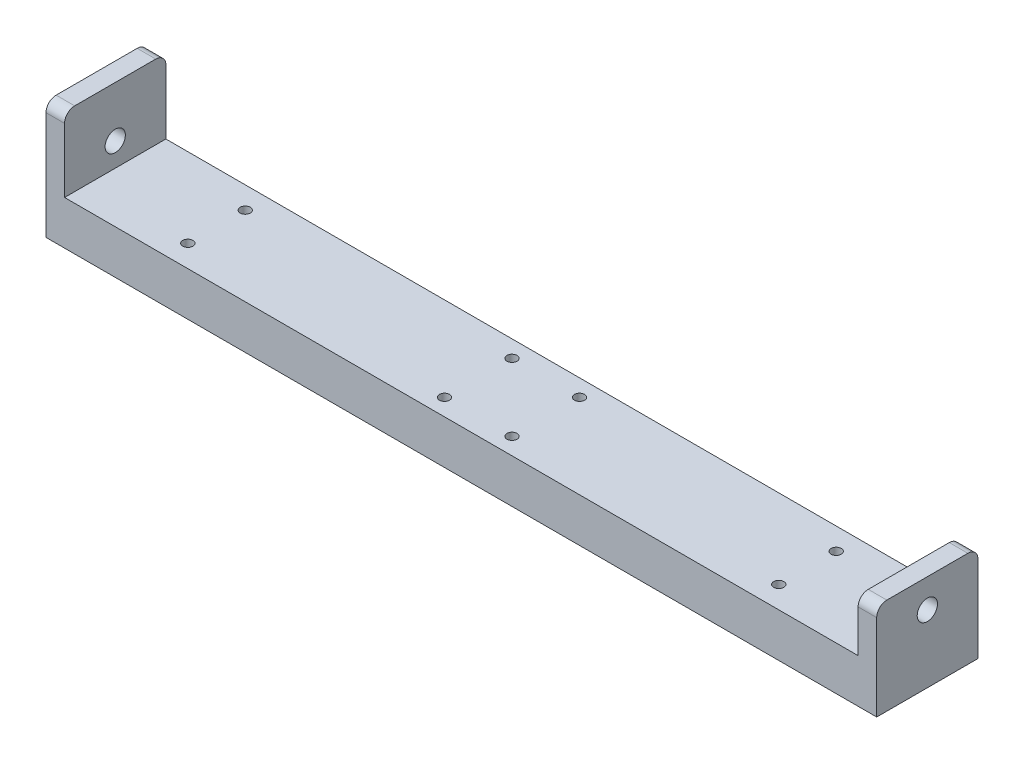
SolidWorks part; units mm, degrees
material "普通碳钢"
ref_plane "前视基准面" through (0, 0, 0) normal (0, 0, 1) x (1, 0, 0)
ref_plane "上视基准面" through (0, 0, 0) normal (0, 1, 0) x (1, 0, 0)
ref_plane "右视基准面" through (0, 0, 0) normal (1, 0, 0) x (0, 0, -1)
sketch "草图1" plane through (0, 0, 0) normal (0, 0, 1) x (1, 0, 0)
  line L0 (0, 0) -> (246, 0)
  line L1 (246, 0) -> (246, 28.5)
  line L2 (246, 28.5) -> (240.5, 28.5)
  line L3 (240.5, 28.5) -> (240.5, 13)
  line L4 (240.5, 13) -> (5.5, 13)
  line L5 (5.5, 13) -> (5.5, 35)
  line L6 (5.5, 35) -> (0, 35)
  line L7 (0, 35) -> (0, 0)
  dimension "D1" = 5.5
  dimension "D2" = 35
  dimension "D3" = 28.5
  dimension "D4" = 13
  dimension "D5" = 246
  dimension "D6" = 5.5
extrude "凸台-拉伸1" add sketch "草图1" along normal mid plane 30
sketch "草图2" plane through (0, 13, 0) normal (0, 1, 0) x (1, 0, 0)
  line L0 (0, 0) -> (246, 0) construction
  line L1 (246, -15) -> (246, 15) construction
  line L2 (123, 0) -> (123, 15) construction
  line L3 (240.5, 15) -> (5.5, 15) construction
  line L4 (5.5, -15) -> (5.5, 15) construction
  circle A0 centre (35.5, 8.5) radius 1.5
  circle A1 centre (210.5, 8.5) radius 1.5
  circle A2 centre (35.5, -8.5) radius 1.5
  circle A3 centre (210.5, -8.5) radius 1.5
  circle A4 centre (113, 10) radius 1.5
  circle A5 centre (133, 10) radius 1.5
  circle A6 centre (133, -10) radius 1.5
  circle A7 centre (113, -10) radius 1.5
  point P23 (114.5, 6.9981)
  dimension "D3" = 3
  dimension "D4" = 3
  dimension "D1" = 8.5
  dimension "D2" = 30
  dimension "D5" = 10
  dimension "D6" = 10
extrude "切除-拉伸1" cut sketch "草图2" against normal up to next
fillet "圆角2" radius 3 4 edges at (243.25, 28.5, -15) (243.25, 28.5, 15) (2.75, 35, -15) (2.75, 35, 15)
sketch "草图3" plane through (0, 0, 0) normal (-1, 0, 0) x (0, 0, 1)
  line L0 (0, 35) -> (0, 0) construction
  line L1 (12, 35) -> (-12, 35) construction
  line L2 (15, 0) -> (-15, 0) construction
  circle A0 centre (0, 20) radius 3
  dimension "D2" = 6
  dimension "D1" = 20
extrude "切除-拉伸2" cut sketch "草图3" against normal through all
